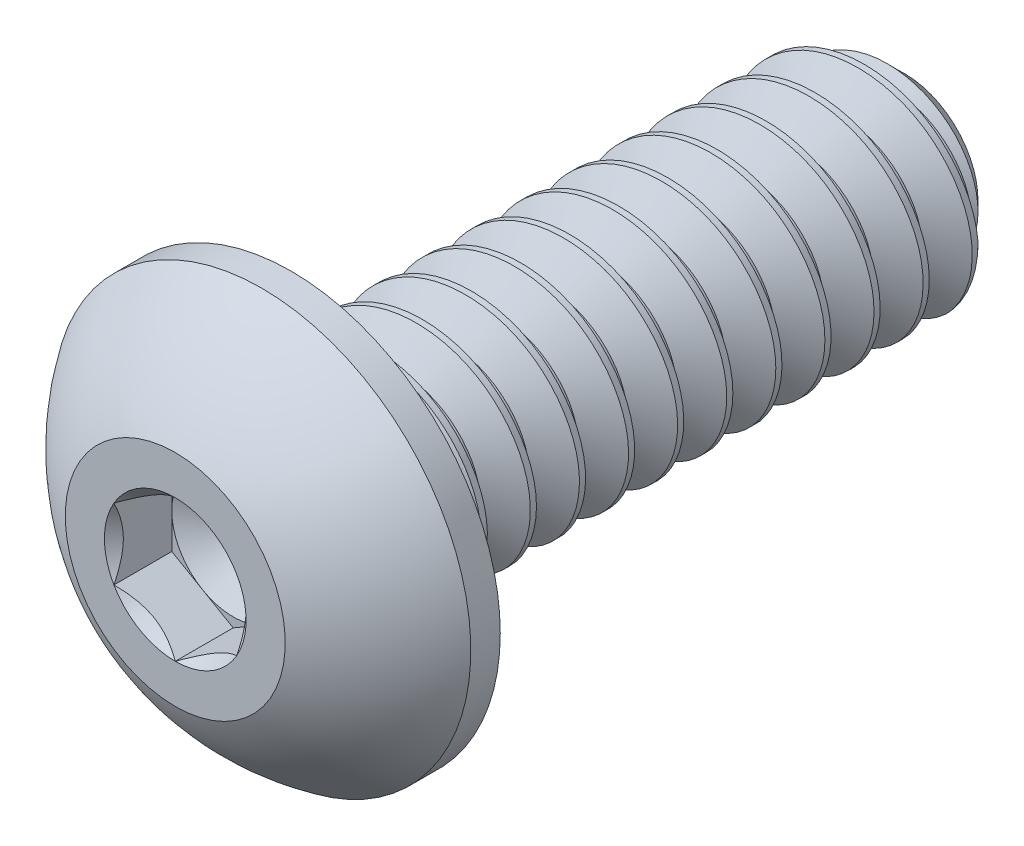
SolidWorks part; units mm, degrees
ref_plane "Front" through (0, 0, 0) normal (0, 0, 1) x (1, 0, 0)
ref_plane "Top" through (0, 0, 0) normal (0, 1, 0) x (1, 0, 0)
ref_plane "Right" through (0, 0, 0) normal (1, 0, 0) x (0, 0, -1)
sketch "Sketch1" plane through (0, 0, 0) normal (1, 0, 0) x (0, 0, -1)
  line L0 (0, 0) -> (-1.4986, 0) construction
  line L1 (0, 0) -> (7.9375, 0)
  line L2 (0, 0) -> (0, 1.4224)
  line L3 (0, 1.4224) -> (7.9375, 1.4224)
  line L4 (7.9375, 0) -> (7.9375, 1.4224)
  line L5 (0, -1.4224) -> (7.9375, -1.4224) construction
  dimension "D1" = 7.9375
  dimension "Thread Dia" = 2.8448
  dimension "Length" = 7.9375
  dimension "Head Height" = 1.4986
revolve "Revolve1" add sketch "Sketch1" angle 360 about L0
ref_plane "Plane1" through (0, 0, 1.4986) normal (0, 0, 1) x (1, 0, 0)
chamfer "Chamfer1" distance 0.4763 angle 45 1 edges at (0, 1.4224, -7.9375)
sketch "Sketch10" plane through (0, 0, 0) normal (1, 0, 0) x (0, 0, -1)
  line L0 (7.9375, 1.4224) -> (8.4931, 1.4224)
  line L1 (8.4931, 1.4224) -> (8.255, 1.01)
  line L2 (8.255, 1.01) -> (8.1756, 1.01)
  line L3 (8.1756, 1.01) -> (7.9375, 1.4224)
  line L4 (8.0566, 1.2162) -> (8.3741, 1.2162) construction
  dimension "D1" = 60
  dimension "D2" = 0.0794
  dimension "D3" = 0.3175
sketch "Sketch11" plane through (0, 0, -7.9375) normal (0, 0, -1) x (-1, 0, 0)
  circle A1 centre (0, 0) radius 0.9462
  circle A2 centre (0, 0) radius 0.9462
  dimension "D1" = 0
curve "Helix/Spiral1" pitch 0.635 height 11.1125 turns 17.5
sweep "Cut-Sweep1" cut profiles "Sketch10" path "Helix/Spiral1"
sketch "Sketch4" plane through (0, 0, 0) normal (0, 0, 1) x (1, 0, 0)
  circle A0 centre (0, 0) radius 2.7051
  dimension "Head Dia" = 5.4102
extrude "Extrude1" add sketch "Sketch4" along normal up to surface (1.4986 mm away) up to plane "Plane1"
sketch "Sketch9" plane through (0, 0, 0) normal (1, 0, 0) x (0, 0, -1)
  line L0 (0, 2.7051) -> (-0.381, 2.7051)
  line L1 (0, 2.7051) -> (0, 3.0861)
  line L2 (0, 3.0861) -> (-1.8796, 3.0861)
  line L3 (0, 0) -> (-1.4986, 0) construction
  line L4 (-1.8796, 3.0861) -> (-1.8796, 1.4224)
  line L5 (-1.8796, 1.4224) -> (-1.4986, 1.4224)
  line L6 (0, 0) -> (0, 1.4224) construction
  line L10 (0, 2.7051) -> (-1.4986, 2.7051) construction
  line L11 (0, 1.4224) -> (7.9375, 1.4224) construction
  line L12 (-1.4986, 2.7051) -> (-1.4986, -2.7051) construction
  arc A0 (-1.4986, 1.4224) -> (-0.381, 2.7051) centre (1.4288, 0) cw
  dimension "Side Head Height" = 0.381
revolve "Cut-Revolve3" cut sketch "Sketch9" angle 360 about L3
sketch "Sketch6" plane through (0, 0, 1.4986) normal (0, 0, 1) x (1, 0, 0)
  line L1 (0, -0.9165) -> (0.7937, -0.4583)
  line L2 (0.7937, -0.4583) -> (0.7937, 0.4583)
  line L3 (0.7937, 0.4583) -> (0, 0.9165)
  line L4 (0, 0.9165) -> (-0.7938, 0.4583)
  line L5 (-0.7938, 0.4583) -> (-0.7938, -0.4583)
  line L6 (-0.7938, -0.4583) -> (0, -0.9165)
  circle A0 centre (0, 0) radius 0.7938 construction
  dimension "Hex" = 1.5875
extrude "Cut-Extrude1" cut sketch "Sketch6" against normal blind 0.7493
sketch "Sketch7" plane through (0, 0, 1.4986) normal (0, 0, 1) x (1, 0, 0)
  circle A0 centre (0, 0) radius 0.9165
extrude "Cut-Extrude4" cut sketch "Sketch7" against normal blind 0.7493 draft 45
sketch "Sketch8" plane through (0, 0, 0.7493) normal (0, 0, 1) x (1, 0, 0)
  circle A0 centre (0, 0) radius 0.7938 construction
  circle A1 centre (0, 0) radius 0.7938
extrude "Cut-Extrude5" cut sketch "Sketch8" against normal blind 0.2498 draft 60
sketch "Sketch12" plane through (0, 0, 0) normal (1, 0, 0) x (0, 0, -1)
  line L1 (0, -1.4224) -> (7.9375, -1.4224) construction
  spline S0 degree 2 poles (7.4612, 0.013) (7.4194, 0.5945) (7.3819, 1.0058) (7.329, 1.5865) (7.276, 1.3739) (7.2231, 1.1614) (7.1702, 0.3681) (7.1173, -0.4251) (7.0644, -1.0058) (7.0115, -1.5865) (6.9585, -1.3739) (6.9056, -1.1614) (6.8527, -0.3681) (6.7998, 0.4251) (6.7469, 1.0058) (6.694, 1.5865) (6.641, 1.3739) (6.5881, 1.1614) (6.5352, 0.3681) (6.4823, -0.4251) (6.4294, -1.0058) (6.3765, -1.5865) (6.3235, -1.3739) (6.2706, -1.1614) (6.2177, -0.3681) (6.1648, 0.4251) (6.1119, 1.0058) (6.059, 1.5865) (6.006, 1.3739) (5.9531, 1.1614) (5.9002, 0.3681) (5.8473, -0.4251) (5.7944, -1.0058) (5.7415, -1.5865) (5.6885, -1.3739) (5.6356, -1.1614) (5.5827, -0.3681) (5.5298, 0.4251) (5.4769, 1.0058) (5.424, 1.5865) (5.371, 1.3739) (5.3181, 1.1614) (5.2652, 0.3681) (5.2123, -0.4251) (5.1594, -1.0058) (5.1065, -1.5865) (5.0535, -1.3739) (5.0006, -1.1614) (4.9477, -0.3681) (4.8948, 0.4251) (4.8419, 1.0058) (4.789, 1.5865) (4.736, 1.3739) (4.6831, 1.1614) (4.6302, 0.3681) (4.5773, -0.4251) (4.5244, -1.0058) (4.4715, -1.5865) (4.4185, -1.3739) (4.3656, -1.1614) (4.3127, -0.3681) (4.2598, 0.4251) (4.2069, 1.0058) (4.154, 1.5865) (4.101, 1.3739) (4.0481, 1.1614) (3.9952, 0.3681) (3.9423, -0.4251) (3.8894, -1.0058) (3.8365, -1.5865) (3.7835, -1.3739) (3.7306, -1.1614) (3.6777, -0.3681) (3.6248, 0.4251) (3.5719, 1.0058) (3.519, 1.5865) (3.466, 1.3739) (3.4131, 1.1614) (3.3602, 0.3681) (3.3073, -0.4251) (3.2544, -1.0058) (3.2015, -1.5865) (3.1485, -1.3739) (3.0956, -1.1614) (3.0427, -0.3681) (2.9898, 0.4251) (2.9369, 1.0058) (2.884, 1.5865) (2.831, 1.3739) (2.7781, 1.1614) (2.7252, 0.3681) (2.6723, -0.4251) (2.6194, -1.0058) (2.5665, -1.5865) (2.5135, -1.3739) (2.4606, -1.1614) (2.4077, -0.3681) (2.3548, 0.4251) (2.3019, 1.0058) (2.249, 1.5865) (2.196, 1.3739) (2.1431, 1.1614) (2.0902, 0.3681) (2.0373, -0.4251) (1.9844, -1.0058) (1.9315, -1.5865) (1.8785, -1.3739) (1.8256, -1.1614) (1.7727, -0.3681) (1.7198, 0.4251) (1.6669, 1.0058) (1.614, 1.5865) (1.561, 1.3739) (1.5081, 1.1614) (1.4552, 0.3681) (1.4023, -0.4251) (1.3494, -1.0058) (1.2965, -1.5865) (1.2435, -1.3739) (1.1906, -1.1614) (1.1377, -0.3681) (1.0848, 0.4251) (1.0319, 1.0058) (0.979, 1.5865) (0.926, 1.3739) (0.8731, 1.1614) (0.8202, 0.3681) (0.7673, -0.4251) (0.7144, -1.0058) (0.6615, -1.5865) (0.6085, -1.3739) (0.5556, -1.1614) (0.5027, -0.3681) (0.4498, 0.4251) (0.3969, 1.0058) (0.344, 1.5865) (0.291, 1.3739) (0.2381, 1.1614) (0.1852, 0.3681) (0.1323, -0.4251) (0.0794, -1.0058) (0.0419, -1.417) (0, -1.4223) knots 0.048731 0.048731 0.048731 0.055556 0.055556 0.064815 0.064815 0.074074 0.074074 0.083333 0.083333 0.092593 0.092593 0.101852 0.101852 0.111111 0.111111 0.12037 0.12037 0.12963 0.12963 0.138889 0.138889 0.148148 0.148148 0.157407 0.157407 0.166667 0.166667 0.175926 0.175926 0.185185 0.185185 0.194444 0.194444 0.203704 0.203704 0.212963 0.212963 0.222222 0.222222 0.231481 0.231481 0.240741 0.240741 0.25 0.25 0.259259 0.259259 0.268519 0.268519 0.277778 0.277778 0.287037 0.287037 0.296296 0.296296 0.305556 0.305556 0.314815 0.314815 0.324074 0.324074 0.333333 0.333333 0.342593 0.342593 0.351852 0.351852 0.361111 0.361111 0.37037 0.37037 0.37963 0.37963 0.388889 0.388889 0.398148 0.398148 0.407407 0.407407 0.416667 0.416667 0.425926 0.425926 0.435185 0.435185 0.444444 0.444444 0.453704 0.453704 0.462963 0.462963 0.472222 0.472222 0.481481 0.481481 0.490741 0.490741 0.5 0.5 0.509259 0.509259 0.518519 0.518519 0.527778 0.527778 0.537037 0.537037 0.546296 0.546296 0.555556 0.555556 0.564815 0.564815 0.574074 0.574074 0.583333 0.583333 0.592593 0.592593 0.601852 0.601852 0.611111 0.611111 0.62037 0.62037 0.62963 0.62963 0.638889 0.638889 0.648148 0.648148 0.657407 0.657407 0.666667 0.666667 0.675926 0.675926 0.685185 0.685185 0.694444 0.694444 0.701269 0.701269 0.701269 weights 0.948065 0.901259 1 0.866025 1 0.866025 1 0.866025 1 0.866025 1 0.866025 1 0.866025 1 0.866025 1 0.866025 1 0.866025 1 0.866025 1 0.866025 1 0.866025 1 0.866025 1 0.866025 1 0.866025 1 0.866025 1 0.866025 1 0.866025 1 0.866025 1 0.866025 1 0.866025 1 0.866025 1 0.866025 1 0.866025 1 0.866025 1 0.866025 1 0.866025 1 0.866025 1 0.866025 1 0.866025 1 0.866025 1 0.866025 1 0.866025 1 0.866025 1 0.866025 1 0.866025 1 0.866025 1 0.866025 1 0.866025 1 0.866025 1 0.866025 1 0.866025 1 0.866025 1 0.866025 1 0.866025 1 0.866025 1 0.866025 1 0.866025 1 0.866025 1 0.866025 1 0.866025 1 0.866025 1 0.866025 1 0.866025 1 0.866025 1 0.866025 1 0.866025 1 0.866025 1 0.866025 1 0.866025 1 0.866025 1 0.866025 1 0.866025 1 0.866025 1 0.866025 1 0.866025 1 0.866025 1 0.866025 1 0.866025 1 0.901259 0.948065 construction
  point P0 (6.9841, -1.4224)
equation "\"D1@Cut-Extrude1\"=\"Head Height@Sketch1\"/2"
equation "\"D1@Cut-Extrude4\"=\"D1@Cut-Extrude1\""
equation "\"D1@Cut-Extrude5\"=\"D1@Cut-Extrude1\"/3"
equation "\"D3@Helix/Spiral1\" = \"Length@Sketch1\" + .125"
equation "\"D1@Chamfer1\" = \"D4@Helix/Spiral1\" * .75"
equation "\"D2@Sketch10\" = \"D4@Helix/Spiral1\" * .125"
equation "\"D3@Sketch10\" = \"D4@Helix/Spiral1\" * .5"
